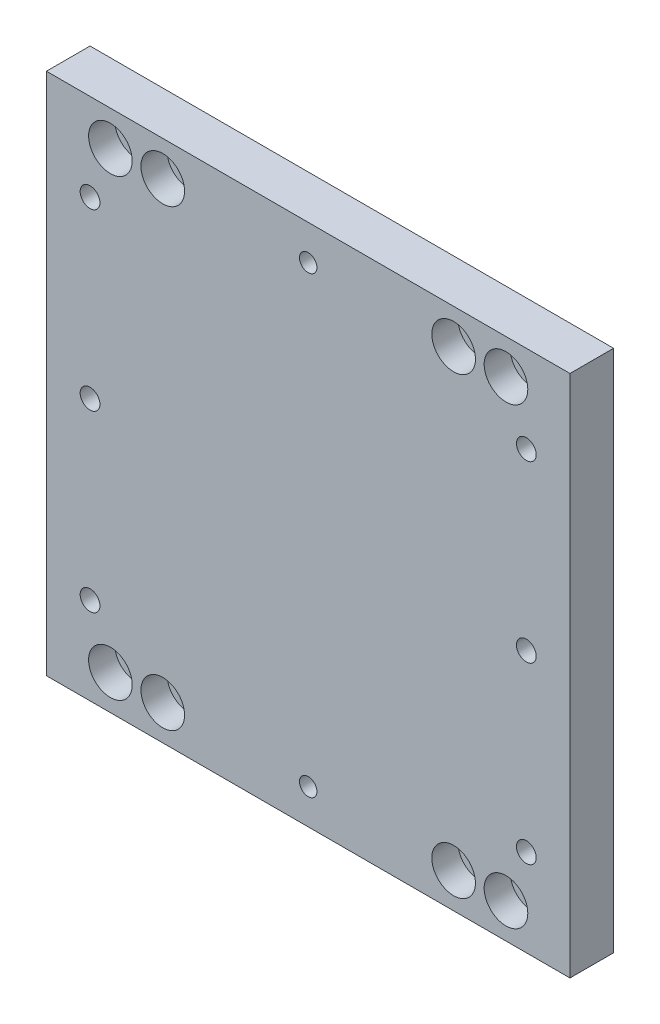
SolidWorks part; units mm, degrees
ref_plane "前视基准面" through (0, 0, 0) normal (0, 0, 1) x (1, 0, 0)
ref_plane "上视基准面" through (0, 0, 0) normal (0, 1, 0) x (1, 0, 0)
ref_plane "右视基准面" through (0, 0, 0) normal (1, 0, 0) x (0, 0, -1)
sketch "草图1" plane through (0, 0, 0) normal (0, 0, 1) x (1, 0, 0)
  line L1 (-90, 90) -> (90, 90)
  line L2 (-90, 90) -> (-90, -90)
  line L3 (-90, -90) -> (90, -90)
  line L4 (90, 90) -> (90, -90)
  dimension "D1" = 180
  dimension "D2" = 180
  dimension "D3" = 90
  dimension "D4" = 90
extrude "凸台-拉伸1" add sketch "草图1" along normal blind 15
sketch "草图2" plane through (0, 0, 15) normal (0, 0, 1) x (1, 0, 0)
  line L0 (-68, 78) -> (-68, -82.6003) construction
  line L1 (-68, 78) -> (68, 78) construction
  line L2 (68, 78) -> (68, -78) construction
  line L3 (68, -78) -> (-94.1662, -78) construction
  line L4 (-50, 86.5454) -> (-50, -78.741) construction
  line L5 (50, 78) -> (50, -78) construction
  line L7 (0, 78) -> (0, -78) construction
  line L8 (90, 90) -> (-90, 90) construction
  dimension "D1" = 136
  dimension "D2" = 100
  dimension "D3" = 50
  dimension "D4" = 68
  dimension "D5" = 156
  dimension "D6" = 12
hole_wizard "打孔尺寸根据内六角花形圆柱头螺钉-4.8级的类型1" positions "3D草图1" profile "草图3" counterbore size "M14" standard "Gb" end condition through all
sketch3d "3D草图1"
  line L0 (-68, 78, 15) -> (-68, -82.6003, 15) construction
  line L1 (68, -78, 15) -> (-94.1662, -78, 15) construction
  line L2 (-68, 78, 15) -> (68, 78, 15) construction
  line L3 (-50, 86.5454, 15) -> (-50, -78.741, 15) construction
  point P0 (-68, -78, 15)
  point P6 (-50, -78, 15)
  point P8 (50, -78, 15)
  point P11 (68, -78, 15)
  point P14 (68, 78, 15)
  point P17 (50, 78, 15)
  point P20 (-50, 78, 15)
  point P26 (-68, 78, 15)
sketch "草图3" plane through (-68, -78, 15) normal (1, 0, 0) x (0, -1, 0)
  line L0 (0, 0) -> (0, 15)
  line L1 (0, 15) -> (4.5, 15)
  line L3 (4.5, 15) -> (4.5, 9)
  line L4 (4.5, 9) -> (7.5, 9)
  line L5 (7.5, 9) -> (7.5, 0)
  line L7 (7.5, 0) -> (0, 0)
  line L11 (0, -6.35) -> (0, 107.95) construction
  dimension "通孔孔直径" = 9
  dimension "通孔孔深度" = 15
  dimension "柱形沉头孔直径" = 15
  dimension "柱形沉头孔深度" = 9
hole_wizard "Ø6.0 (6) 直径孔1" positions "3D草图2" profile "草图4" hole size "Ø6.0" standard "Gb" end condition through all
sketch3d "3D草图2"
  point P0 (0, 78, 15)
  point P3 (0, -78, 15)
sketch "草图4" plane through (0, 78, 15) normal (1, 0, 0) x (0, -1, 0)
  line L0 (0, 0) -> (0, 15)
  line L1 (0, 15) -> (3, 15)
  line L2 (3, 15) -> (3, 0)
  line L5 (3, 0) -> (0, 0)
  line L11 (0, -6.35) -> (0, 107.95) construction
  dimension "通孔孔直径" = 6
  dimension "通孔孔深度" = 15
sketch "草图8" plane through (0, 0, 15) normal (0, 0, 1) x (1, 0, 0)
  line L0 (-75, 60) -> (75, 60) construction
  line L1 (75, 60) -> (75, -60) construction
  line L2 (75, -60) -> (-75, -60) construction
  line L3 (-75, -60) -> (-75, 60) construction
  line L4 (90, -90) -> (90, 90) construction
  line L5 (-75, 0) -> (75, 0) construction
  dimension "D1" = 150
  dimension "D2" = 15
  dimension "D3" = 120
  dimension "D4" = 60
hole_wizard "M8 螺纹孔1" positions "3D草图4" profile "草图9" tap size "M8" standard "Gb"
sketch3d "3D草图4"
  point P0 (-75, 60, 15)
  point P3 (-75, 0, 15)
  point P6 (-75, -60, 15)
  point P9 (75, -60, 15)
  point P12 (75, 0, 15)
  point P15 (75, 60, 15)
sketch "草图9" plane through (-75, 60, 15) normal (1, 0, 0) x (0, -1, 0)
  line L0 (0, 0) -> (0, 24.2929)
  line L1 (0, 24.2929) -> (3.4, 22.25)
  line L2 (3.4, 22.25) -> (3.4, 0)
  line L5 (3.4, 0) -> (0, 0)
  line L10 (0, 24.2929) -> (-3.4, 22.25) construction
  line L11 (0, -6.35) -> (0, 107.95) construction
  dimension "螺纹孔钻头直径" = 6.8
  dimension "螺纹孔钻头深度" = 22.25
  dimension "导头角度" = 118
cosmetic thread "孔螺蚊线1" parameters "D1"=15, "D2"=8
cosmetic thread "孔螺蚊线2" parameters "D1"=15, "D2"=8
cosmetic thread "孔螺蚊线3" parameters "D1"=15, "D2"=8
cosmetic thread "孔螺蚊线4" parameters "D1"=15, "D2"=8
cosmetic thread "孔螺蚊线5" parameters "D1"=15, "D2"=8
cosmetic thread "孔螺蚊线6" parameters "D1"=15, "D2"=8
